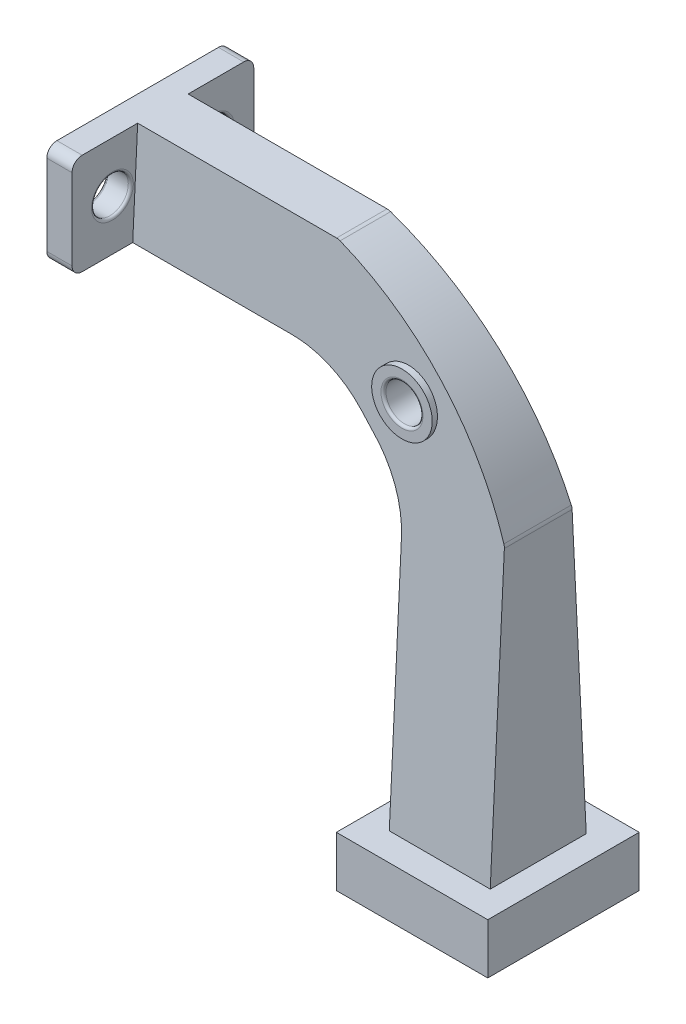
SolidWorks part; units mm, degrees
ref_plane "Front Plane" through (0, 0, 0) normal (0, 0, 1) x (1, 0, 0)
ref_plane "Top Plane" through (0, 0, 0) normal (0, 1, 0) x (1, 0, 0)
ref_plane "Right Plane" through (0, 0, 0) normal (1, 0, 0) x (0, 0, -1)
sketch "Sketch1" plane through (0, 0, 0) normal (0, 0, 1) x (1, 0, 0)
  line L0 (-25.1969, 29.2075) -> (-3.1164, 29.2075) construction
  line L1 (12.4969, -29.2075) -> (12.4969, 13.5943) construction
  line L2 (12.4969, 13.5943) -> (-3.1164, 29.2075) construction
  line L3 (25.1969, -29.2075) -> (25.1969, 13.5943) construction
  line L4 (25.1969, 13.5943) -> (9.5836, 29.2075) construction
  line L5 (9.5836, 29.2075) -> (-3.1164, 29.2075) construction
  line L6 (12.4969, -29.2075) -> (25.1969, -29.2075)
  line L9 (25.1969, -29.2075) -> (25.1969, 13.5943)
  line L10 (25.1969, 13.5943) -> (3.2336, 35.5575) construction
  line L11 (3.2336, 35.5575) -> (-25.1969, 35.5575)
  line L12 (-25.1969, 35.5575) -> (-25.1969, 22.8575)
  line L13 (-25.1969, 22.8575) -> (3.2336, 22.8575)
  line L14 (3.2336, 22.8575) -> (12.4969, 13.5943)
  line L15 (12.4969, 13.5943) -> (12.4969, -29.2075)
  arc A0 (3.2336, 35.5575) -> (25.1969, 13.5943) centre (-9.5936, 0.7671) cw
  point P25 (-25.1969, 29.2075)
  dimension "D1" = 45
  dimension "D2" = 12.7
  dimension "D7" = 45
extrude "Boss-Extrude1" add sketch "Sketch1" along normal mid plane 12.7
sketch "Sketch17" plane through (-25.1969, 0, 0) normal (-1, 0, 0) x (0, 0, 1)
  line L0 (6.35, -29.2075) -> (3.175, 35.5575)
  line L1 (6.35, 35.5575) -> (-6.35, 35.5575) construction
  line L2 (3.175, 35.5575) -> (-3.175, 35.5575)
  line L3 (-3.175, 35.5575) -> (-6.35, -29.2075)
  line L4 (-6.35, -29.2075) -> (6.35, -29.2075)
  dimension "D1" = 3.175
  dimension "D2" = 3.175
extrude "Cut-Extrude5" cut sketch "Sketch17" against normal through all from offset 3.175 flip side to cut offset against normal yes
sketch "Sketch18" plane through (0, 0, 0) normal (0, 0, 1) x (1, 0, 0)
  line L1 (-25.1969, 35.5575) -> (-22.0219, 35.5575)
  line L2 (-25.1969, 35.5575) -> (-25.1969, 22.8575)
  line L3 (-25.1969, 22.8575) -> (-22.0219, 22.8575)
  line L4 (-22.0219, 35.5575) -> (-22.0219, 22.8575)
extrude "Boss-Extrude7" add sketch "Sketch18" along normal blind 5.08 from surface starting at face at (-23.6094, 29.2075, 6.35)
extrude "Boss-Extrude8" add sketch "Sketch18<2>" against normal blind 5.08 from surface starting at face at (-23.6094, 29.2075, -6.35)
sketch "Sketch18<2>" plane through (0, 0, 0) normal (0, 0, 1) x (1, 0, 0) same geometry as "Sketch18"
sketch "Sketch20" plane through (0, 0, 0) normal (0, 0, 1) x (1, 0, 0)
  circle A0 centre (12.4969, 22.8575) radius 2.3241
  circle A1 centre (12.4969, 22.8575) radius 3.81
  dimension "D1" = 4.6482
  dimension "D2" = 7.62
extrude "Cut-Extrude6" cut sketch "Sketch20" against normal through all both and the other way through all contours A0
fillet "Fillet7" radius 12.7 2 edges at (12.4969, 13.5943, 0) (3.2336, 22.8575, 0)
fillet "Fillet9" radius 1.27 6 edges at (25.1969, 13.5943, 0) (3.2336, 35.5575, 0) (-23.6094, 22.8575, 11.43) (-23.6094, 22.8575, -11.43) (-23.6094, 35.5575, -11.43) (-23.6094, 35.5575, 11.43)
extrude "Boss-Extrude9" add sketch "Sketch20<4>" along normal mid plane 8.89
sketch "Sketch20<4>" plane through (0, 0, 0) normal (0, 0, 1) x (1, 0, 0) same geometry as "Sketch20"
fillet "Fillet10" radius 0.3175 2 edges at (14.821, 22.8575, -4.445) (14.821, 22.8575, 4.445)
sketch "Sketch21" plane through (-25.1969, 0, 0) normal (-1, 0, 0) x (0, 0, 1)
  line L0 (-11.43, 29.2075) -> (11.43, 29.2075) construction
  line L1 (-11.43, 24.1275) -> (-11.43, 34.2875) construction
  line L2 (11.43, 34.2875) -> (11.43, 24.1275) construction
  point P6 (-6.35, 29.2075)
  point P7 (6.35, 29.2075)
  point P8 (0, 0)
  dimension "D1" = 5.08
  dimension "D2" = 5.08
hole_wizard "#14 (0.182) Diameter Hole1" positions "Sketch21" profile "Sketch22" hole size "#14" standard "ANSI Inch" end condition through all
sketch "Sketch22" plane through (-25.1969, 29.2075, 6.35) normal (0, 1, 0) x (0, 0, 1)
  line L0 (0, 0) -> (0, 50.3937)
  line L1 (0, 50.3937) -> (2.3114, 50.3937)
  line L2 (2.3114, 50.3937) -> (2.3114, 0)
  line L5 (2.3114, 0) -> (0, 0)
  line L11 (0, -6.35) -> (0, 107.95) construction
  dimension "Thru Hole Dia." = 4.6228
  dimension "Thru Hole Depth" = 50.3937
fillet "Fillet11" radius 0.3175 4 edges at (-22.0219, 26.8961, 6.35) (-25.1969, 29.2075, 8.6614) (-22.0219, 26.8961, -6.35) (-25.1969, 29.2075, -4.0386)
sketch "Sketch23" plane through (0, -29.2075, 0) normal (0, -1, 0) x (1, 0, 0)
  line L0 (12.4969, -6.35) -> (25.1969, 6.35) construction
  circle A1 centre (18.8469, 0) radius 2.3241
  point P4 (18.8469, 0)
  dimension "D1" = 4.6482
extrude "Cut-Extrude7" cut sketch "Sketch23" against normal blind 12.7
sketch "Sketch25" plane through (0, -29.2075, 0) normal (0, -1, 0) x (1, 0, 0)
  line L0 (12.4969, 6.35) -> (25.1969, 6.35) construction
  line L1 (20.68, 3.175) -> (17.0138, 3.175)
  line L2 (17.0138, 3.175) -> (15.1807, 0) construction
  line L3 (15.1807, 0) -> (17.0138, -3.175) construction
  line L4 (17.0138, -3.175) -> (20.68, -3.175)
  line L5 (20.68, -3.175) -> (22.513, 0)
  line L6 (22.513, 0) -> (20.68, 3.175)
  line L10 (17.0138, 3.175) -> (4.6825, 3.175)
  line L11 (4.6825, 3.175) -> (4.6825, -3.175)
  line L12 (4.6825, -3.175) -> (17.0138, -3.175)
  circle A0 centre (18.8469, 0) radius 3.175 construction
  dimension "D1" = 6.35
extrude "Cut-Extrude8" cut sketch "Sketch25" against normal blind 6.604 from offset 6.35 offset against normal yes
sketch "Sketch26" plane through (0, -29.2075, 0) normal (0, -1, 0) x (1, 0, 0)
  line L1 (9.3219, -9.525) -> (28.3719, -9.525)
  line L2 (9.3219, -9.525) -> (9.3219, 9.525)
  line L3 (9.3219, 9.525) -> (28.3719, 9.525)
  line L4 (28.3719, -9.525) -> (28.3719, 9.525)
  line L5 (9.3219, -9.525) -> (28.3719, 9.525) construction
  line L6 (9.3219, 9.525) -> (28.3719, -9.525) construction
  circle A0 centre (18.8469, 0) radius 4.25
  point P0 (18.8469, 0)
  dimension "D1" = 19.05
extrude "Boss-Extrude10" add sketch "Sketch26" against normal blind 6.35
